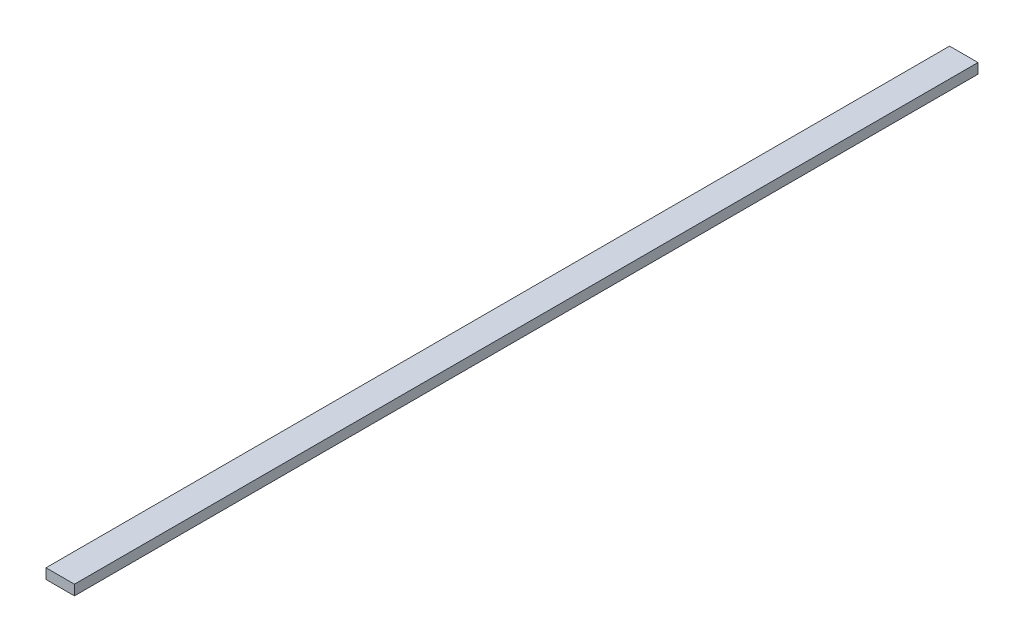
SolidWorks part; units mm, degrees
ref_plane "Ebene vorne" through (0, 0, 0) normal (0, 0, 1) x (1, 0, 0)
ref_plane "Ebene oben" through (0, 0, 0) normal (0, 1, 0) x (1, 0, 0)
ref_plane "Ebene rechts" through (0, 0, 0) normal (1, 0, 0) x (0, 0, -1)
sketch "Skizze1" plane through (0, 0, 0) normal (0, 0, 1) x (1, 0, 0)
  line L1 (0, 0) -> (14, 0)
  line L2 (0, 0) -> (0, 5)
  line L3 (0, 5) -> (14, 5)
  line L4 (14, 0) -> (14, 5)
  point P4 (0, 0)
  dimension "D1" = 5
  dimension "D2" = 14
extrude "Aufsatz-Linear austragen1" add sketch "Skizze1" along normal blind 445
